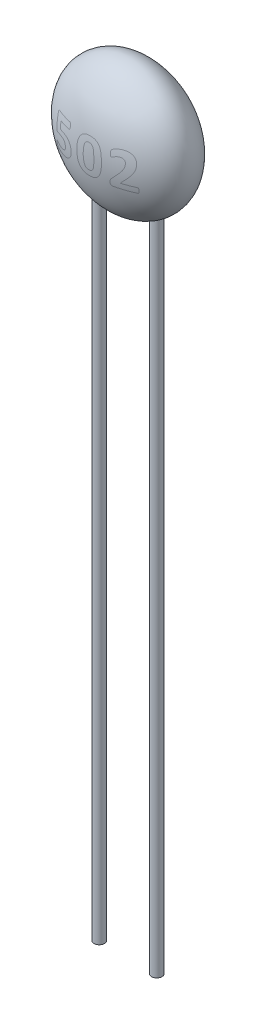
SolidWorks part; units mm, degrees
material "6061-T6 (SS)"
ref_plane "Front Plane" through (0, 0, 0) normal (0, 0, 1) x (1, 0, 0)
ref_plane "Top Plane" through (0, 0, 0) normal (0, 1, 0) x (1, 0, 0)
ref_plane "Right Plane" through (0, 0, 0) normal (1, 0, 0) x (0, 0, -1)
sketch "Sketch1" plane through (0, 0, 0) normal (1, 0, 0) x (0, 0, -1)
  line L0 (-1.75, 0) -> (1.75, 0)
  line L1 (0, 0) -> (0, -2.9) construction
  ellipse E0 centre (0, 0) end of major axis (0, -2.9) minor radius 1.75 (1.75, 0) -> (-1.75, 0) ccw
  dimension "D1" = 5.8
  dimension "D2" = 3.5
revolve "Revolve1" add sketch "Sketch1" angle 360 about L0
ref_plane "Plane1" through (0, 0, 2) normal (0, 0, 1) x (1, 0, 0)
sketch "Sketch2" plane through (0, 0, 2) normal (0, 0, 1) x (1, 0, 0)
  line L0 (0, 0.75) -> (0, -0.75) construction
  line L2 (-2.5, 0.75) -> (2.5, 0.75) construction
  line L3 (-2.5, 0.75) -> (-2.5, -0.75) construction
  line L4 (-2.5, -0.75) -> (2.5, -0.75) construction
  line L5 (2.5, 0.75) -> (2.5, -0.75) construction
  text T0 "502" font "Calibri" height 1.5
  dimension "D1" = 1.5
  dimension "D2" = 5
wrap "Wrap1" sketch "Sketch2" wrap type scribe source sketch "Sketch2"
sketch "Sketch3" plane through (0, 0, 0) normal (0, 1, 0) x (1, 0, 0)
  line L0 (-1.27, 0) -> (1.27, 0) construction
  circle A0 centre (-1.27, 0) radius 0.23
  circle A1 centre (1.27, 0) radius 0.23
  dimension "D2" = 0.46
  dimension "D1" = 2.54
extrude "Boss-Extrude1" add sketch "Sketch3" against normal blind 31.5
